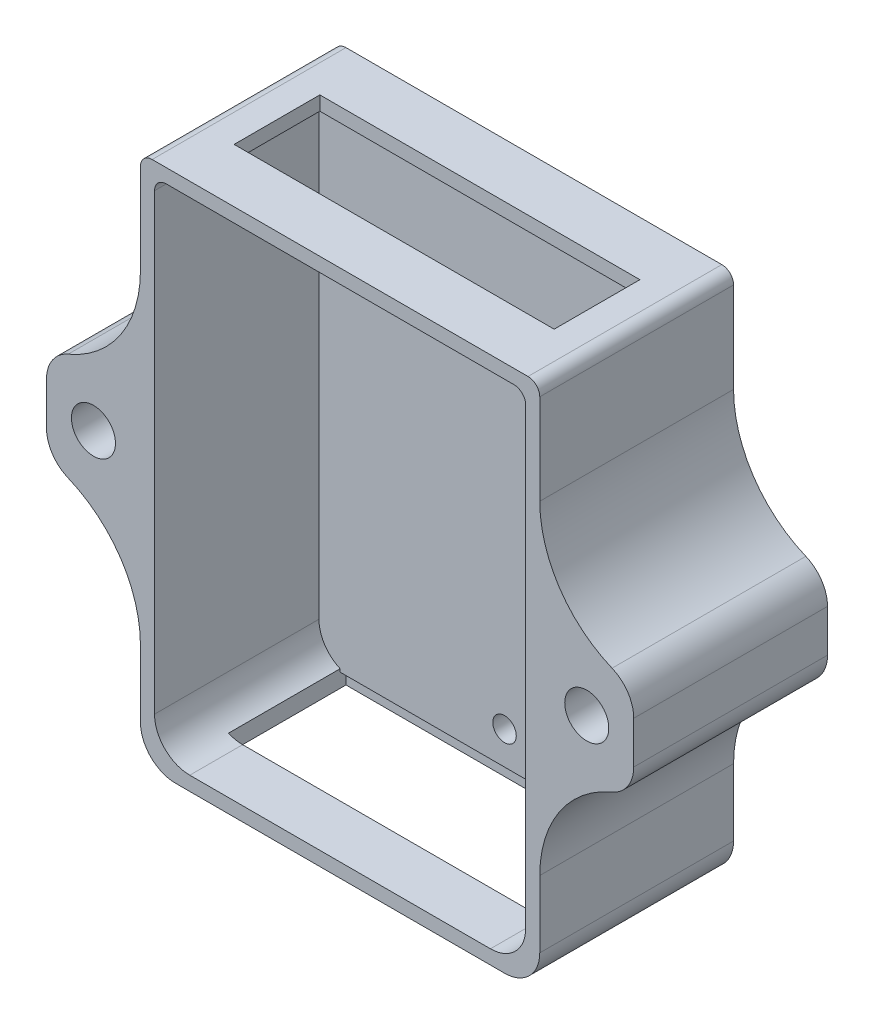
SolidWorks part; units mm, degrees
ref_plane "Front Plane" through (0, 0, 0) normal (0, 0, 1) x (1, 0, 0)
ref_plane "Top Plane" through (0, 0, 0) normal (0, 1, 0) x (1, 0, 0)
ref_plane "Right Plane" through (0, 0, 0) normal (1, 0, 0) x (0, 0, -1)
sketch "Sketch1" plane through (0, 0, 0) normal (0, 0, 1) x (1, 0, 0)
  line L0 (17, 52.832) -> (17, 18.8808) construction
  line L1 (0, 0) -> (34, 0)
  line L2 (0, 0) -> (0, 45)
  line L3 (0, 45) -> (34, 45)
  line L4 (34, 0) -> (34, 45)
  circle A0 centre (17, 4) radius 1
  point P9 (17, 0)
  point P10 (17, 45)
  dimension "D4" = 2
  dimension "D1" = 4
  dimension "D2" = 45
  dimension "D3" = 34
extrude "Boss-Extrude1" add sketch "Sketch1" along normal blind 2.5
sketch "Sketch2" plane through (0, 0, 2.5) normal (0, 0, 1) x (1, 0, 0)
  line L0 (1.2, 1.2) -> (1.2, 43.8)
  line L1 (0, 0) -> (34, 0)
  line L2 (0, 0) -> (0, 45)
  line L3 (0, 45) -> (34, 45)
  line L4 (34, 0) -> (34, 45)
  line L5 (1.2, 43.8) -> (32.8, 43.8)
  line L6 (32.8, 1.2) -> (32.8, 43.8)
  line L7 (1.2, 1.2) -> (32.8, 1.2)
  dimension "D1" = 1.2
extrude "Boss-Extrude2" add sketch "Sketch2" along normal blind 14
sketch "Sketch7" plane through (0, 0, 0) normal (0, -1, 0) x (-1, 0, 0)
  line L0 (-17, -16.5) -> (-17, 0) construction
  line L1 (0, -16.5) -> (-34, -16.5) construction
  line L2 (0, 0) -> (-34, 0) construction
  line L3 (-17, 0) -> (-17, -8.25) construction
  line L4 (-17, -8.25) -> (-34, -8.25) construction
  line L5 (-34, -16.5) -> (-34, 0) construction
  line L6 (-34, -8.25) -> (0, -8.25) construction
  line L7 (0, -16.5) -> (0, 0) construction
  line L9 (-3, -2) -> (-31, -2)
  line L10 (-3, -2) -> (-3, -12)
  line L11 (-3, -12) -> (-31, -12)
  line L12 (-31, -2) -> (-31, -12)
  line L13 (-3, -2) -> (-31, -12) construction
  line L14 (-3, -12) -> (-31, -2) construction
  point P13 (-17, -7)
  dimension "D1" = 10
  dimension "D2" = 1.25
  dimension "D3" = 3
  dimension "D4" = 3
extrude "Cut-Extrude2" cut sketch "Sketch7" against normal up to surface (1.2 mm away) up to face at (17, 1.2, 9.5)
sketch "Sketch9" plane through (0, 45, 0) normal (0, 1, 0) x (1, 0, 0)
  line L0 (0, -8.25) -> (34, -8.25) construction
  line L1 (0, -16.5) -> (0, 0) construction
  line L2 (34, -16.5) -> (34, 0) construction
  line L3 (34, -8.25) -> (34, 0) construction
  line L4 (34, 0) -> (17, 0) construction
  line L5 (34, 0) -> (0, 0) construction
  line L6 (17, 0) -> (17, -16.5) construction
  line L7 (34, -16.5) -> (0, -16.5) construction
  line L9 (3.375, -11.9) -> (30.625, -11.9)
  line L10 (3.375, -11.9) -> (3.375, -4.6)
  line L11 (3.375, -4.6) -> (30.625, -4.6)
  line L12 (30.625, -11.9) -> (30.625, -4.6)
  line L13 (3.375, -11.9) -> (30.625, -4.6) construction
  line L14 (3.375, -4.6) -> (30.625, -11.9) construction
  point P14 (17, -8.25)
  dimension "D1" = 7.3
  dimension "D2" = 27.25
extrude "Cut-Extrude3" cut sketch "Sketch9" against normal up to next
sketch "Sketch10" plane through (0, 0, 0) normal (0, 0, -1) x (-1, 0, 0)
  line L0 (-34, 22.5) -> (0, 22.5) construction
  line L1 (0, 22.5) -> (0, 45) construction
  line L2 (-17, 45) -> (-17, 0) construction
  line L3 (-42, 22.5) -> (-34, 22.5) construction
  line L4 (0, 0) -> (0, 45)
  line L5 (0, 45) -> (-34, 45)
  line L6 (-34, 45) -> (-34, 0)
  line L7 (-34, 0) -> (0, 0)
  line L8 (0, 0) -> (0, 45)
  line L9 (0, 45) -> (-34, 45)
  line L10 (-34, 45) -> (-34, 0)
  line L11 (-34, 0) -> (0, 0)
  line L12 (-34, 18.5) -> (-42, 18.5)
  line L13 (-34, 18.5) -> (-34, 26.5)
  line L14 (-34, 26.5) -> (-42, 26.5)
  line L15 (-42, 18.5) -> (-42, 26.5)
  line L16 (0, 18.5) -> (8, 18.5)
  line L17 (0, 18.5) -> (0, 26.5)
  line L18 (0, 26.5) -> (8, 26.5)
  line L19 (8, 18.5) -> (8, 26.5)
  line L20 (0, 22.5) -> (8, 22.5) construction
  circle A0 centre (-38, 22.5) radius 1.875
  circle A1 centre (4, 22.5) radius 1.875
  point P16 (-42, 22.5)
  point P18 (-38, 22.5)
  point P20 (4, 22.5)
  dimension "D3" = 3.75
  dimension "D2" = 8
  dimension "D4" = 8
  dimension "D1" = 0
extrude "Boss-Extrude3" add sketch "Sketch10" against normal up to surface (16.5 mm away) contours L15 L12 L10 L14 A0 | L16 L19 L18 L8 A1 region at (-0.1131, 22.5, 0) region at (38, 18.6131, 0) up to face at (17, 22.5, 16.5)
fillet "Fillet1" radius 10 4 edges
fillet "Fillet2" radius 3 8 edges at (34, 0, 8.25) (32.8, 1.2, 9.5) (1.2, 1.2, 9.5) (0, 0, 8.25) (42, 26.5, 8.25) (42, 18.5, 8.25) (-8, 26.5, 8.25) (-8, 18.5, 8.25)
fillet "Fillet3" radius 1 4 edges at (32.8, 43.8, 9.5) (1.2, 43.8, 9.5) (34, 45, 8.25) (0, 45, 8.25)
sketch "Sketch11" plane through (0, 0, 0) normal (0, 0, -1) x (-1, 0, 0)
  line L1 (-38, 19.1802) -> (-35.125, 20.8401)
  line L2 (-35.125, 20.8401) -> (-35.125, 24.1599)
  line L3 (-35.125, 24.1599) -> (-38, 25.8198)
  line L4 (-38, 25.8198) -> (-40.875, 24.1599)
  line L5 (-40.875, 24.1599) -> (-40.875, 20.8401)
  line L6 (-40.875, 20.8401) -> (-38, 19.1802)
  line L7 (4, 19.1802) -> (6.875, 20.8401)
  line L8 (6.875, 20.8401) -> (6.875, 24.1599)
  line L9 (6.875, 24.1599) -> (4, 25.8198)
  line L10 (4, 25.8198) -> (1.125, 24.1599)
  line L11 (1.125, 24.1599) -> (1.125, 20.8401)
  line L12 (1.125, 20.8401) -> (4, 19.1802)
  circle A0 centre (-38, 22.5) radius 2.875 construction
  circle A1 centre (4, 22.5) radius 2.875 construction
  dimension "D1" = 5.75
extrude "Cut-Extrude4" cut sketch "Sketch11" against normal blind 3
chamfer "Chamfer1" distance 3 angle 30 2 edges at (-5.875, 22.5, 3) (36.125, 22.5, 3) first distance on face at (-5.875, 22.5, 16.5) first distance on face at (36.125, 22.5, 16.5)
sketch "Sketch13" plane through (0, 0, 16.5) normal (0, 0, 1) x (1, 0, 0)
  line L8 (34, 36.298) -> (34, 44)
  line L9 (33, 45) -> (1, 45)
  line L10 (0, 44) -> (0, 36.298)
  line L11 (-8, 24.298) -> (-8, 20.702)
  line L12 (0, 8.702) -> (0, 3)
  line L13 (3, 0) -> (31, 0)
  line L14 (34, 3) -> (34, 8.702)
  line L15 (42, 20.702) -> (42, 24.298)
  line L16 (34, 36.298) -> (34, 44)
  line L17 (33, 45) -> (1, 45)
  line L18 (0, 44) -> (0, 36.298)
  line L19 (-8, 24.298) -> (-8, 20.702)
  line L20 (0, 8.702) -> (0, 3)
  line L21 (3, 0) -> (31, 0)
  line L22 (34, 3) -> (34, 8.702)
  line L23 (42, 20.702) -> (42, 24.298)
  circle A0 centre (17, 4) radius 1
  circle A1 centre (17, 4) radius 1 construction
  circle A2 centre (-4, 22.5) radius 1.875 construction
  circle A3 centre (-4, 22.5) radius 1.875
  circle A4 centre (38, 22.5) radius 1.875 construction
  circle A5 centre (38, 22.5) radius 1.875
  arc A12 (34, 44) -> (33, 45) centre (33, 44) ccw
  arc A13 (1, 45) -> (0, 44) centre (1, 44) ccw
  arc A14 (-6.1538, 27.0672) -> (0, 36.298) centre (-10, 36.298) ccw
  arc A15 (-6.1538, 27.0672) -> (-8, 24.298) centre (-5, 24.298) ccw
  arc A16 (-8, 20.702) -> (-6.1538, 17.9328) centre (-5, 20.702) ccw
  arc A17 (0, 8.702) -> (-6.1538, 17.9328) centre (-10, 8.702) ccw
  arc A18 (0, 3) -> (3, 0) centre (3, 3) ccw
  arc A19 (31, 0) -> (34, 3) centre (31, 3) ccw
  arc A20 (40.1538, 17.9328) -> (34, 8.702) centre (44, 8.702) ccw
  arc A21 (40.1538, 17.9328) -> (42, 20.702) centre (39, 20.702) ccw
  arc A22 (42, 24.298) -> (40.1538, 27.0672) centre (39, 24.298) ccw
  arc A23 (34, 36.298) -> (40.1538, 27.0672) centre (44, 36.298) ccw
  arc A24 (34, 44) -> (33, 45) centre (33, 44) ccw
  arc A25 (1, 45) -> (0, 44) centre (1, 44) ccw
  arc A26 (-6.1538, 27.0672) -> (0, 36.298) centre (-10, 36.298) ccw
  arc A27 (-6.1538, 27.0672) -> (-8, 24.298) centre (-5, 24.298) ccw
  arc A28 (-8, 20.702) -> (-6.1538, 17.9328) centre (-5, 20.702) ccw
  arc A29 (0, 8.702) -> (-6.1538, 17.9328) centre (-10, 8.702) ccw
  arc A30 (0, 3) -> (3, 0) centre (3, 3) ccw
  arc A31 (31, 0) -> (34, 3) centre (31, 3) ccw
  arc A32 (40.1538, 17.9328) -> (34, 8.702) centre (44, 8.702) ccw
  arc A33 (40.1538, 17.9328) -> (42, 20.702) centre (39, 20.702) ccw
  arc A34 (42, 24.298) -> (40.1538, 27.0672) centre (39, 24.298) ccw
  arc A35 (34, 36.298) -> (40.1538, 27.0672) centre (44, 36.298) ccw
  dimension "D1" = 0
